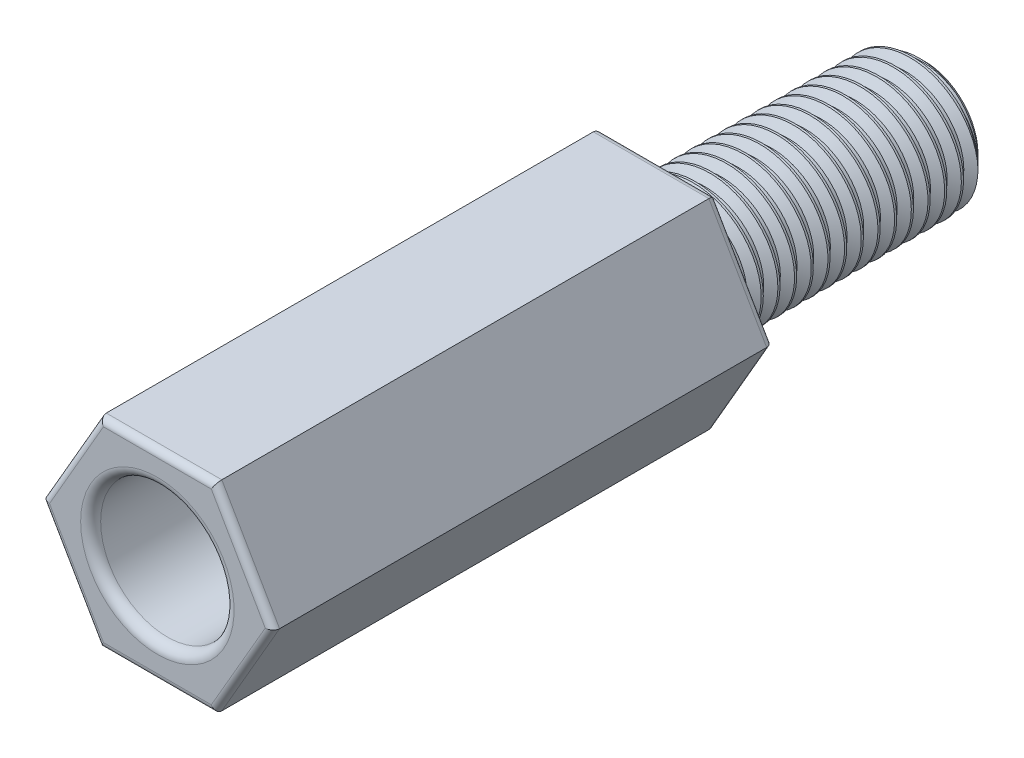
SolidWorks part; units mm, degrees
ref_plane "Front Plane" through (0, 0, 0) normal (0, 0, 1) x (1, 0, 0)
ref_plane "Top Plane" through (0, 0, 0) normal (0, 1, 0) x (1, 0, 0)
ref_plane "Right Plane" through (0, 0, 0) normal (1, 0, 0) x (0, 0, -1)
ref_axis "Axis1" through (0, 0, -5.8251) along (0, 0, 1)
sketch "Sketch1" plane through (0, 0, 0) normal (0, 0, 1) x (1, 0, 0)
  line L1 (3.4641, 0) -> (1.7321, 3)
  line L2 (1.7321, 3) -> (-1.7321, 3)
  line L3 (-1.7321, 3) -> (-3.4641, 0)
  line L4 (-3.4641, 0) -> (-1.7321, -3)
  line L5 (-1.7321, -3) -> (1.7321, -3)
  line L6 (1.7321, -3) -> (3.4641, 0)
  circle A0 centre (0, 0) radius 3 construction
  dimension "D1" = 6
extrude "Boss-Extrude1" add sketch "Sketch1" along normal blind 15
sketch "Эскиз1" plane through (0, 0, 0) normal (0, 1, 0) x (1, 0, 0)
  line L0 (0, -15) -> (0, -5.9721)
  line L1 (0, -5.9721) -> (2, -6.7)
  line L2 (2, -6.7) -> (2, -14.7)
  line L3 (2.3, -15) -> (0, -15)
  line L4 (1.7321, -15) -> (3.4641, -15) construction
  line L5 (0, 0) -> (0, -5.9721) construction
  arc A0 (2, -14.7) -> (2.3, -15) centre (2.3, -14.7) ccw
  dimension "D2" = 0.3
  dimension "D1" = 8
  dimension "D3" = 4
  dimension "D4" = 70
revolve "Вырез-Повернуть1" cut sketch "Эскиз1" angle 360 about L5
sketch "Эскиз2" plane through (0, 0, 0) normal (0, 1, 0) x (1, 0, 0)
  line L0 (0, 0) -> (0, 19.4698) construction
  line L1 (0, 0) -> (1.6, 0)
  line L2 (1.6, 0) -> (1.6, 0.2)
  line L3 (1.6, 0.2) -> (2, 0.4309)
  line L4 (2, 0.4309) -> (2, 7.6)
  line L5 (2, 7.6) -> (1.6, 8)
  line L6 (1.6, 8) -> (0, 8)
  line L7 (0, 8) -> (0, 0)
  dimension "D1" = 4
  dimension "D2" = 8
  dimension "D3" = 0.2
  dimension "D4" = 3.2
  dimension "D5" = 60
  dimension "D6" = 45
revolve "Повернуть1" add sketch "Эскиз2" angle 360 about L0
thread "Резьба1" pitch 0.5 method cut profile "Профиль резьбы1" start angle 0, offset 1, length 0, pitch 0.5, diameter 4
ref_plane "Плоскость1" through (2, 0, -8.6) normal (0, -1, 0) x (1, 0, 0)
sketch "Профиль резьбы1" plane through (2, 0, -8.6) normal (0, -1, 0) x (1, 0, 0)
  line L0 (0, 0) -> (0, 0.5) construction
  line L11 (0, 0) -> (0, 0.4375)
  line L12 (0, 0.4375) -> (-0.2706, 0.2812)
  line L13 (-0.2706, 0.2812) -> (-0.2706, 0.1562)
  line L15 (-0.2706, 0.1562) -> (0, 0)
  line L17 (-0.2706, 0.2187) -> (0, 0.2187) construction
  point P2 (0, 0)
  dimension "Pitch" = 0.5
  dimension "Profile_Angle" = 60
  dimension "Profile_Land" = 0.125
  dimension "Profile_Height" = 0.2706
fillet "Fillet2" radius 0.2 12 edges at (-2.5981, 1.5, 15) (-2.5981, -1.5, 15) (0, -3, 15) (2.5981, -1.5, 15) (2.5981, 1.5, 15) (0, 3, 15) (2.5981, -1.5, 0) (0, -3, 0) (-2.5981, -1.5, 0) (-2.5981, 1.5, 0) (0, 3, 0) (2.5981, 1.5, 0)
